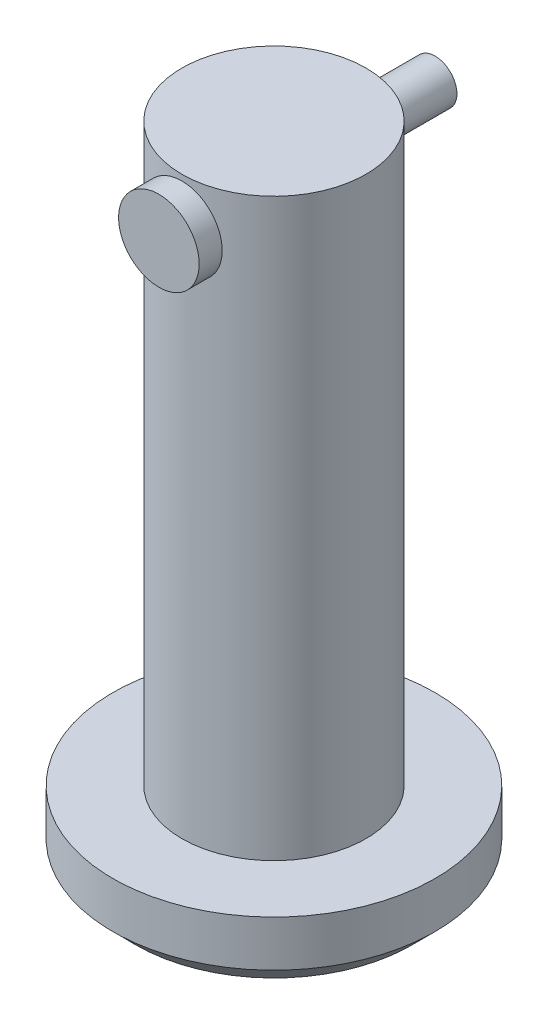
SolidWorks part; units mm, degrees
ref_plane "Front Plane" through (0, 0, 0) normal (0, 0, 1) x (1, 0, 0)
ref_plane "Top Plane" through (0, 0, 0) normal (0, 1, 0) x (1, 0, 0)
ref_plane "Right Plane" through (0, 0, 0) normal (1, 0, 0) x (0, 0, -1)
sketch "Sketch1" plane through (0, 0, 0) normal (0, 1, 0) x (1, 0, 0)
  circle A0 centre (0, 0) radius 4
extrude "Boss-Extrude1" add sketch "Sketch1" along normal blind 25
sketch "Sketch2" plane through (0, 0, 0) normal (0, -1, 0) x (1, 0, 0)
  circle A0 centre (0, 0) radius 7
  dimension "D1" = 14
extrude "Boss-Extrude2" add sketch "Sketch2" along normal blind 3
chamfer "Chamfer1" distance 1 angle 45 1 edges at (0, -3, -7)
sketch "Sketch3" plane through (0, 0, 0) normal (0, 0, 1) x (1, 0, 0)
  line L0 (4, 25) -> (-4, 25) construction
  circle A0 centre (0, 23) radius 1
  dimension "D1" = 2
  dimension "D2" = 2
extrude "Cut-Extrude1" cut sketch "Sketch3" against normal blind 10 and the other way blind 10
sketch "Sketch4" plane through (0, 0, 0) normal (0, 0, 1) x (1, 0, 0)
  circle A0 centre (0, 23) radius 0.95
  dimension "D1" = 1.9
extrude "Boss-Extrude3" add sketch "Sketch4" along normal blind 5 and the other way blind 7 separate body
sketch "Sketch5" plane through (0, 0, 5) normal (0, 0, 1) x (1, 0, 0)
  circle A0 centre (0, 23) radius 1.75
  dimension "D1" = 3.5
extrude "Boss-Extrude4" add sketch "Sketch5" against normal blind 1
